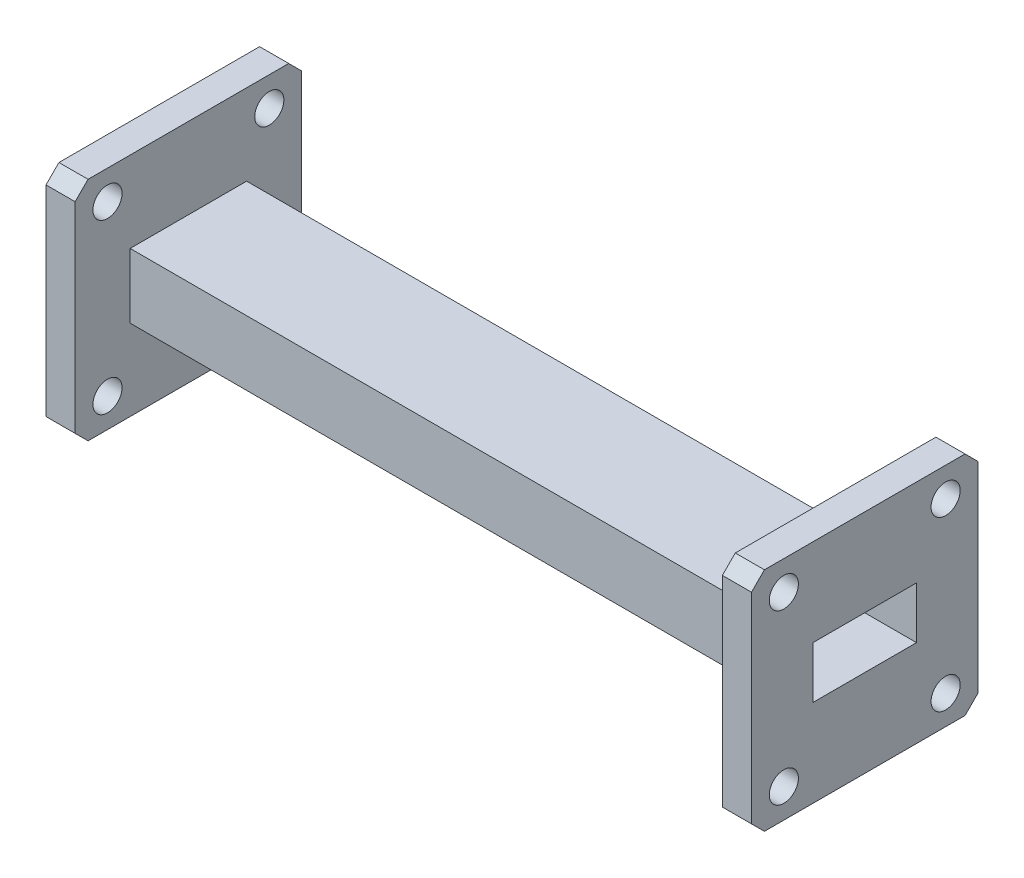
SolidWorks part; units mm, degrees
ref_plane "Спереди" through (0, 0, 0) normal (0, 0, 1) x (1, 0, 0)
ref_plane "Сверху" through (0, 0, 0) normal (0, 1, 0) x (1, 0, 0)
ref_plane "Справа" through (0, 0, 0) normal (1, 0, 0) x (0, 0, -1)
sketch "Эскиз1" plane through (0, 0, 0) normal (1, 0, 0) x (0, 0, -1)
  line L1 (-17.5, -17.5) -> (17.5, -17.5)
  line L2 (-17.5, -17.5) -> (-17.5, 17.5)
  line L3 (-17.5, 17.5) -> (17.5, 17.5)
  line L4 (17.5, -17.5) -> (17.5, 17.5)
  line L5 (-17.5, -17.5) -> (17.5, 17.5) construction
  line L6 (-17.5, 17.5) -> (17.5, -17.5) construction
  line L7 (-8, -4) -> (8, -4)
  line L8 (-8, -4) -> (-8, 4)
  line L9 (-8, 4) -> (8, 4)
  line L10 (8, -4) -> (8, 4)
  line L11 (-8, -4) -> (8, 4) construction
  line L12 (-8, 4) -> (8, -4) construction
  point P0 (0, 0)
  point P6 (0, 0)
  dimension "D1" = 35
  dimension "D2" = 35
  dimension "D3" = 8
  dimension "D4" = 16
extrude "Бобышка-Вытянуть1" add sketch "Эскиз1" along normal blind 4.5
sketch "Эскиз2" plane through (0, 0, 0) normal (-1, 0, 0) x (0, 0, 1)
  point P0 (12.5, 13)
  dimension "D1" = 12.5
  dimension "D2" = 13
ref_axis "Ось1" through (-53.9761, 0, 0) along (1, 0, 0)
chamfer "Фаска1" distance 2 4 edges at (2.25, -17.5, 17.5) (2.25, -17.5, -17.5) (2.25, 17.5, -17.5) (2.25, 17.5, 17.5)
sketch "Эскиз4" plane through (4.5, 0, 0) normal (1, 0, 0) x (0, 0, -1)
  line L1 (-8, -4) -> (8, -4)
  line L2 (-8, -4) -> (-8, 4)
  line L3 (-8, 4) -> (8, 4)
  line L4 (8, -4) -> (8, 4)
  line L5 (-8, -4) -> (8, 4) construction
  line L6 (-8, 4) -> (8, -4) construction
  line L7 (-9, -5) -> (9, -5)
  line L8 (-9, -5) -> (-9, 5)
  line L9 (-9, 5) -> (9, 5)
  line L10 (9, -5) -> (9, 5)
  line L11 (-9, -5) -> (9, 5) construction
  line L12 (-9, 5) -> (9, -5) construction
  point P0 (0, 0)
  point P7 (0, 0)
  dimension "D1" = 1
  dimension "D2" = 1
extrude "Бобышка-Вытянуть2" add sketch "Эскиз4" along normal blind 100
ref_plane "Плоскость4" through (104.5, 0, 0) normal (1, 0, 0) x (0, 0, -1)
sketch "Эскиз5" plane through (104.5, 0, 0) normal (1, 0, 0) x (0, 0, -1)
  line L1 (-17.5, -17.5) -> (17.5, -17.5)
  line L2 (-17.5, -17.5) -> (-17.5, 17.5)
  line L3 (-17.5, 17.5) -> (17.5, 17.5)
  line L4 (17.5, -17.5) -> (17.5, 17.5)
  line L5 (-17.5, -17.5) -> (17.5, 17.5) construction
  line L6 (-17.5, 17.5) -> (17.5, -17.5) construction
  line L7 (-8, -4) -> (8, -4)
  line L8 (-8, -4) -> (-8, 4)
  line L9 (-8, 4) -> (8, 4)
  line L10 (8, -4) -> (8, 4)
  line L11 (-8, -4) -> (8, 4) construction
  line L12 (-8, 4) -> (8, -4) construction
  point P0 (0, 0)
  point P6 (0, 0)
  dimension "D1" = 35
  dimension "D2" = 35
extrude "Бобышка-Вытянуть3" add sketch "Эскиз5" along normal blind 4.5
chamfer "Фаска2" distance 2 angle 45 4 edges at (106.75, -17.5, 17.5) (106.75, -17.5, -17.5) (106.75, 17.5, -17.5) (106.75, 17.5, 17.5)
hole_wizard "Диаметр отверстия Ø4.5 (4.5)2" positions "Трехмерный эскиз2" profile "Эскиз6" hole size "Ø4.5" standard "ISO" end condition through all
sketch3d "Трехмерный эскиз2"
  point P0 (0, 13, 12.5)
sketch "Эскиз6" plane through (0, 13, 12.5) normal (0, 1, 0) x (0, 0, 1)
  line L0 (0, 0) -> (0, 109)
  line L1 (0, 109) -> (2.25, 109)
  line L2 (2.25, 109) -> (2.25, 0)
  line L5 (2.25, 0) -> (0, 0)
  line L11 (0, -6.35) -> (0, 107.95) construction
  dimension "Диаметр сквозного отверстия" = 4.5
  dimension "Глубина сквозного отверстия" = 109
pattern_linear "Линейный массив1" count 2 spacing 25 along (0, 0, -1) count 2 spacing 26 along (0, -1, 0) of "Диаметр отверстия Ø4.5 (4.5)2"
